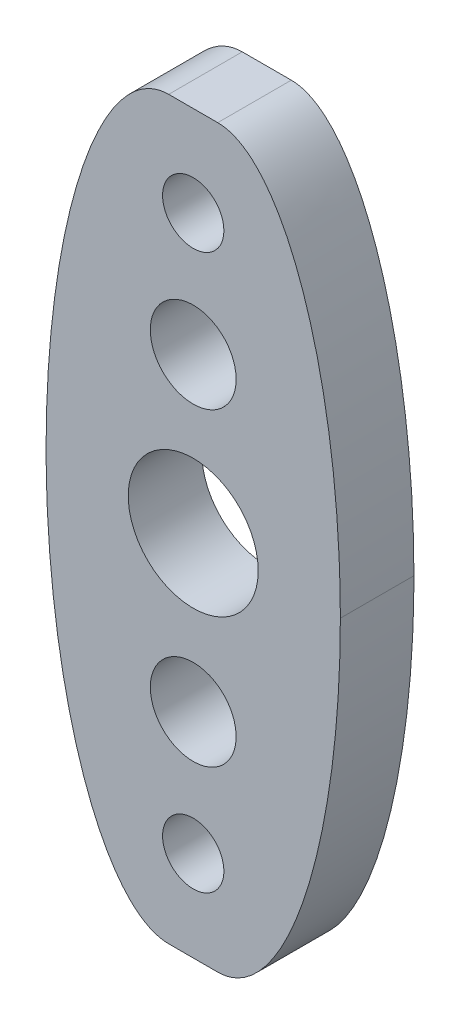
SolidWorks part; units mm, degrees
ref_plane "前视基准面" through (0, 0, 0) normal (0, 0, 1) x (1, 0, 0)
ref_plane "上视基准面" through (0, 0, 0) normal (0, 1, 0) x (1, 0, 0)
ref_plane "右视基准面" through (0, 0, 0) normal (1, 0, 0) x (0, 0, -1)
other "Configuration Table"
sketch "草图1" plane through (0, 0, 0) normal (0, 0, 1) x (1, 0, 0)
  line L0 (1.2363, 12.5657) -> (-10.7637, 12.5657) construction
  line L1 (-10.7637, 27.5657) -> (1.2363, 27.5657)
  line L2 (-10.7637, 27.5657) -> (-10.7637, -2.4343)
  line L3 (-10.7637, -2.4343) -> (1.2363, -2.4343)
  line L4 (1.2363, 27.5657) -> (1.2363, -2.4343)
  line L5 (-4.7637, 27.5657) -> (-4.7637, -2.4343) construction
  circle A0 centre (-4.7637, 12.5657) radius 2.65
  circle A1 centre (-4.7637, 23.8757) radius 1.25
  circle A3 centre (-4.7637, 18.8752) radius 1.75
  circle A4 centre (-4.7637, 1.2557) radius 1.25
  circle A5 centre (-4.7637, 6.2563) radius 1.75
  point P9 (-4.7637, 12.5657)
  dimension "D1" = 5.3
  dimension "D4" = 2.5
  dimension "D5" = 3.5
  dimension "D2" = 12
  dimension "D3" = 30
extrude "凸台-拉伸1" add sketch "草图1" along normal blind 3
fillet "圆角1" radius 5 1 edges at (-10.7637, 27.5657, 1.5) second distance 15 first distance on face at (-4.7637, 27.5657, 1.5)
fillet "圆角2" radius 15 1 edges at (1.2363, 27.5657, 1.5) second distance 5 first distance on face at (1.2363, 12.5657, 1.5)
fillet "圆角3" radius 15 1 edges at (-10.7637, -2.4343, 1.5) second distance 5 first distance on face at (-10.7637, 8.8157, 1.875)
fillet "圆角4" radius 5 1 edges at (1.2363, -2.4343, 1.5) second distance 15 first distance on face at (-4.0137, -2.4343, 1.875)
